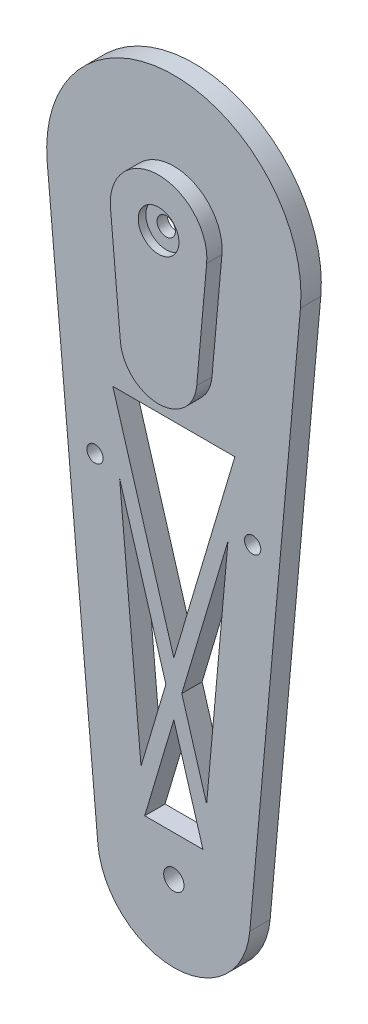
SolidWorks part; units mm, degrees
material "PLA"
ref_plane "Alzado" through (0, 0, 0) normal (0, 0, 1) x (1, 0, 0)
ref_plane "Planta" through (0, 0, 0) normal (0, 1, 0) x (1, 0, 0)
ref_plane "Vista lateral" through (0, 0, 0) normal (1, 0, 0) x (0, 0, -1)
other "PLA"
sketch "Croquis1" plane through (0, 0, 0) normal (0, 0, 1) x (1, 0, 0)
  line L0 (0, 112) -> (0, 0) construction
  line L1 (-14.9401, -1.3393) -> (-25.1002, 112)
  line L2 (14.9401, -1.3393) -> (24.9002, 109.7679)
  line L3 (0, 119.505) -> (19.4147, 119.505) construction
  line L4 (-3.55, 87.955) -> (-3.55, 100.9175)
  line L5 (3.55, 87.955) -> (3.55, 100.9175)
  line L11 (0, 112) -> (0, 123.4883) construction
  line L12 (0.5, 119.4883) -> (0.5, 119.505)
  arc A0 (-14.9401, -1.3393) -> (14.9401, -1.3393) centre (0, 0) ccw
  arc A1 (24.9002, 109.7679) -> (-24.9002, 109.7679) centre (0, 112) ccw
  circle A2 centre (0, 112) radius 7.505
  circle A3 centre (0, 0) radius 2
  circle A4 centre (0, 112) radius 1.65
  arc A5 (0, 84.405) -> (-3.55, 87.955) centre (0, 87.955) cw
  arc A6 (-5.8094, 107.2485) -> (-3.55, 100.9175) centre (-13.55, 100.9175) cw
  arc A7 (5.8094, 107.2485) -> (3.55, 100.9175) centre (13.55, 100.9175) ccw
  arc A8 (0, 84.405) -> (3.55, 87.955) centre (0, 87.955) ccw
  point P26 (0, 79.4404)
  dimension "D1" = 30
  dimension "D2" = 50
  dimension "D4" = 15.01
  dimension "D5" = 4
  dimension "D6" = 3.3
  dimension "D7" = 10
  dimension "D3" = 112
  dimension "D8" = 35.1
  dimension "D9" = 7.1
extrude "Saliente-Extruir1" add sketch "Croquis1" along normal blind 4 contours L2 A1 L1 A0 A2 A3 | A0 region at (0, 64.9983, 0)
ref_plane "Plano1" through (0, 0, 0) normal (1, 0, 0) x (0, -1, 0)
sketch "Croquis11" plane through (0, 0, 0) normal (0, 0, -1) x (-1, 0, 0)
  line L2 (0, 0) -> (0, 137) construction
  line L3 (-10.6804, 11.0037) -> (-15.5, 64.7681) construction
  line L4 (-14.9401, -1.3393) -> (-24.9002, 109.7679) construction
  arc A2 (24.9002, 109.7679) -> (-24.9002, 109.7679) centre (0, 112) ccw construction
  circle A3 centre (-15.5, 64.7681) radius 1.6
  circle A4 centre (15.5, 64.7681) radius 1.6
  dimension "D1" = 31
extrude "Cortar-Extruir1" cut sketch "Croquis11" against normal blind 6 contours A3 | A4
sketch "Croquis12" plane through (0, 0, 4) normal (0, 0, 1) x (1, 0, 0)
  line L0 (0, 79.5266) -> (0, 0) construction
  line L1 (-12, 78) -> (12, 78)
  line L2 (12, 78) -> (5.7249, 8)
  line L3 (5.7249, 8) -> (-5.7249, 8)
  line L4 (-12, 78) -> (-5.7249, 8)
  line L5 (14.9401, -1.3393) -> (24.9002, 109.7679) construction
  line L6 (-6.449, 16.0766) -> (12, 78)
  line L7 (-5.7249, 8) -> (10.6528, 62.9712)
  line L8 (5.7249, 8) -> (-10.6528, 62.9712)
  line L9 (6.449, 16.0766) -> (-12, 78)
  point P5 (10.3575, 64.072)
  point P8 (0, 8)
  point P9 (0, 78)
  point P14 (0, 0)
  point P15 (0, 0)
  point P16 (-4.9932, 8)
  point P17 (0, 0)
  point P18 (-5.7249, 15.2527)
  point P19 (11.0076, 78)
  dimension "D1" = 24
  dimension "D2" = 70
  dimension "D3" = 8
  dimension "D4" = 3
extrude "Cortar-Extruir2" cut sketch "Croquis12" against normal up to next contours L6 L8 L4 | L8 L0 L3 | L0 L7 L3 | L9 L2 L7 | L1 L0 L6 | L0 L1 L9 region at (4, 64.5741, 4) region at (-4, 64.5741, 4) region at (1.9083, 14.4052, 4) region at (-1.9083, 14.4052, 4) region at (-6.2223, 37.1723, 4) region at (6.2223, 37.1723, 4)
sketch "Croquis13" plane through (0, 0, 4) normal (0, 0, 1) x (1, 0, 0)
  line L0 (0, 137) -> (0, -15) construction
  line L2 (7.5014, 89.3498) -> (9.4558, 111.1523)
  line L3 (-7.5014, 89.3498) -> (-9.4558, 111.1523)
  line L4 (14.9401, -1.3393) -> (24.9002, 109.7679) construction
  arc A2 (24.9002, 109.7679) -> (-24.9002, 109.7679) centre (0, 112) ccw construction
  arc A3 (-14.9401, -1.3393) -> (14.9401, -1.3393) centre (0, 0) ccw construction
  arc A4 (-9.4558, 111.1523) -> (9.4558, 111.1523) centre (0, 112) cw
  arc A5 (5.8094, 107.2485) -> (-5.8094, 107.2485) centre (0, 112) ccw construction
  arc A6 (7.5014, 89.3498) -> (-7.5014, 89.3498) centre (0, 90.0222) cw
  circle A7 centre (0, 112) radius 4
  circle A8 centre (0, 112) radius 1.8
  point P15 (7.2124, 87.2647)
  point P16 (10.4381, 111.0643)
  point P17 (10.0978, 111.0948)
  point P20 (0, 0)
  point P21 (7.5014, 89.3498)
  dimension "D1" = 8
  dimension "D2" = 3.6
extrude "Saliente-Extruir2" add sketch "Croquis13" along normal blind 3 contours A6 L3 A4 L2 | A8
extrude "Saliente-Extruir3" add sketch "Croquis13<3>" against normal blind 0.5 contours L0 A7 | A7 | A8 region at (-3.8869, 112, 4)
sketch "Croquis13<3>" plane through (0, 0, 4) normal (0, 0, 1) x (1, 0, 0) same geometry as "Croquis13"
sketch "Croquis14" plane through (0, 0, 7) normal (0, 0, 1) x (1, 0, 0)
  circle A0 centre (0, 112) radius 4
  dimension "D1" = 8
extrude "Cortar-Extruir3" cut sketch "Croquis14" against normal blind 1.5
chamfer "Chaflán1" distance 0.5 angle 45 6 edges at (0, 84.405, 0) (-3.55, 94.4362, 0) (3.55, 94.4362, 0) (4.1318, 104.2785, 0) (-4.1318, 104.2785, 0) (0, 119.505, 0)
sketch "Croquis15" plane through (0, 0, 4) normal (0, 0, -1) x (-1, 0, 0)
  line L0 (0, 137) -> (0, -15) construction
  arc A0 (24.9002, 109.7679) -> (-24.9002, 109.7679) centre (0, 112) ccw construction
  arc A1 (-14.9401, -1.3393) -> (14.9401, -1.3393) centre (0, 0) ccw construction
  circle A2 centre (0, 87.915) radius 1.45
  circle A3 centre (0, 91.915) radius 1.45
  arc A4 (-3.55, 87.955) -> (3.55, 87.955) centre (0, 87.955) ccw construction
  circle A5 centre (0, 91.915) radius 0.75
  circle A6 centre (0, 87.915) radius 0.75
  point P15 (0, 84.405)
  dimension "D1" = 3.51
  dimension "D3" = 2.9
  dimension "D4" = 1.5
  dimension "D2" = 4
extrude "Saliente-Extruir4" add sketch "Croquis15" along normal blind 4
chamfer "Chaflán2" distance 0.2 angle 45 2 edges at (-1.45, 87.915, 0) (-1.45, 91.915, 0)
chamfer "Chaflán3" distance 0.4 angle 45 2 edges at (-1.45, 87.915, 4) (-1.45, 91.915, 4)
